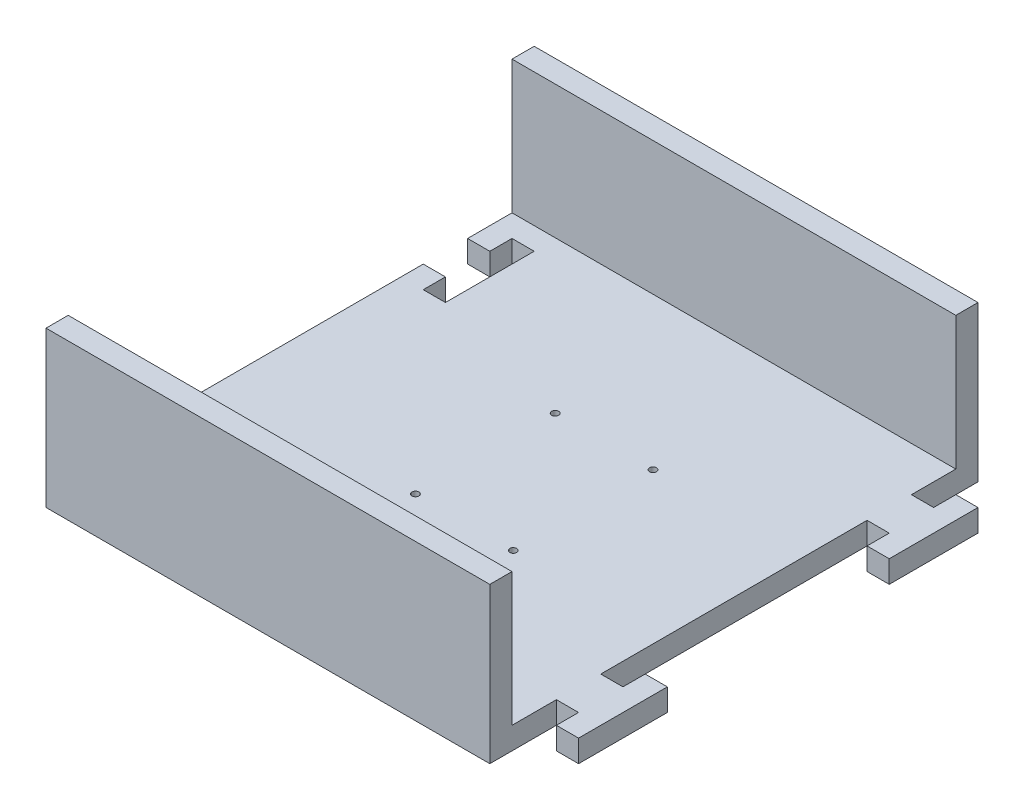
SolidWorks part; units mm, degrees
ref_plane "Front Plane" through (0, 0, 0) normal (0, 0, 1) x (1, 0, 0)
ref_plane "Top Plane" through (0, 0, 0) normal (0, 1, 0) x (1, 0, 0)
ref_plane "Right Plane" through (0, 0, 0) normal (1, 0, 0) x (0, 0, -1)
sketch "Sketch1" plane through (0, 0, 0) normal (0, 1, 0) x (1, 0, 0)
  line L1 (-69.85, -69.85) -> (57.15, -69.85)
  line L2 (-69.85, -69.85) -> (-69.85, 69.85)
  line L3 (-69.85, 69.85) -> (57.15, 69.85)
  line L4 (57.15, -69.85) -> (57.15, 69.85)
  line L5 (-69.85, -69.85) -> (57.15, 69.85) construction
  line L6 (-69.85, 69.85) -> (57.15, -69.85) construction
  point P0 (-6.35, 0)
  dimension "D1" = 127
  dimension "D2" = 139.7
  dimension "D3" = 6.35
extrude "Boss-Extrude1" add sketch "Sketch1" along normal blind 6.35
sketch "Sketch2" plane through (0, 6.35, 0) normal (0, 1, 0) x (1, 0, 0)
  line L1 (-14, -20) -> (14, -20) construction
  line L2 (-14, -20) -> (-14, 20) construction
  line L3 (-14, 20) -> (14, 20) construction
  line L4 (14, -20) -> (14, 20) construction
  line L5 (-14, -20) -> (14, 20) construction
  line L6 (-14, 20) -> (14, -20) construction
  circle A0 centre (-14, 20) radius 1
  circle A1 centre (14, 20) radius 1
  circle A2 centre (14, -20) radius 1
  circle A3 centre (-14, -20) radius 1
  point P0 (0, 0)
  dimension "D3" = 2
  dimension "D1" = 28
  dimension "D2" = 40
extrude "Cut-Extrude1" cut sketch "Sketch2" against normal through all
sketch "Sketch3" plane through (0, 6.35, 0) normal (0, 1, 0) x (1, 0, 0)
  line L0 (57.15, -69.85) -> (57.15, 69.85) construction
  line L1 (-69.85, 69.85) -> (57.15, 69.85)
  line L2 (-69.85, 69.85) -> (-69.85, 63.5)
  line L3 (-69.85, 63.5) -> (57.15, 63.5)
  line L4 (57.15, 69.85) -> (57.15, 63.5)
  line L6 (-69.85, -69.85) -> (57.15, -69.85)
  line L7 (-69.85, -69.85) -> (-69.85, -63.5)
  line L8 (-69.85, -63.5) -> (57.15, -63.5)
  line L9 (57.15, -69.85) -> (57.15, -63.5)
  dimension "D1" = 6.35
extrude "Boss-Extrude2" add sketch "Sketch3" along normal blind 38.1
sketch "Sketch6" plane through (0, 6.35, 0) normal (0, 1, 0) x (1, 0, 0)
  line L0 (57.15, -63.5) -> (57.15, 63.5) construction
  line L1 (57.15, 50.8) -> (63.5, 50.8)
  line L2 (57.15, 50.8) -> (57.15, 38.1)
  line L3 (57.15, 38.1) -> (63.5, 38.1)
  line L5 (57.15, 69.85) -> (-69.85, 69.85) construction
  line L6 (63.5, 57.15) -> (69.85, 57.15)
  line L7 (63.5, 57.15) -> (63.5, 50.8)
  line L8 (63.5, 31.75) -> (69.85, 31.75)
  line L9 (69.85, 57.15) -> (69.85, 31.75)
  line L10 (63.5, 38.1) -> (63.5, 31.75)
  point P10 (69.85, 44.45)
  point P11 (57.15, 44.45)
  dimension "D1" = 6.35
  dimension "D2" = 12.7
  dimension "D3" = 25.4
  dimension "D4" = 6.35
  dimension "D5" = 25.4
extrude "Boss-Extrude3" add sketch "Sketch6" against normal up to surface (6.35 mm away) up to face at (-14, 0, 21)
sketch "Sketch7" plane through (0, 6.35, 0) normal (0, 1, 0) x (1, 0, 0)
  line L0 (-69.85, 63.5) -> (-69.85, -63.5) construction
  line L1 (-69.85, 50.8) -> (-63.5, 50.8)
  line L2 (-69.85, 50.8) -> (-69.85, 38.1)
  line L3 (-69.85, 38.1) -> (-63.5, 38.1)
  line L5 (-63.5, 38.1) -> (-63.5, 31.75)
  line L6 (-57.15, 57.15) -> (-63.5, 57.15)
  line L7 (-57.15, 57.15) -> (-57.15, 31.75)
  line L8 (-57.15, 31.75) -> (-63.5, 31.75)
  line L9 (-63.5, 57.15) -> (-63.5, 50.8)
  line L10 (63.5, 50.8) -> (57.15, 50.8) construction
  line L11 (69.85, 57.15) -> (63.5, 57.15) construction
  line L12 (63.5, 57.15) -> (63.5, 50.8) construction
  line L13 (69.85, 31.75) -> (69.85, 57.15) construction
extrude "Cut-Extrude2" cut sketch "Sketch7" against normal through all
mirror "Mirror1" about plane through (0, 0, 0) normal (0, 0, 1) of "Boss-Extrude3", "Cut-Extrude2"
